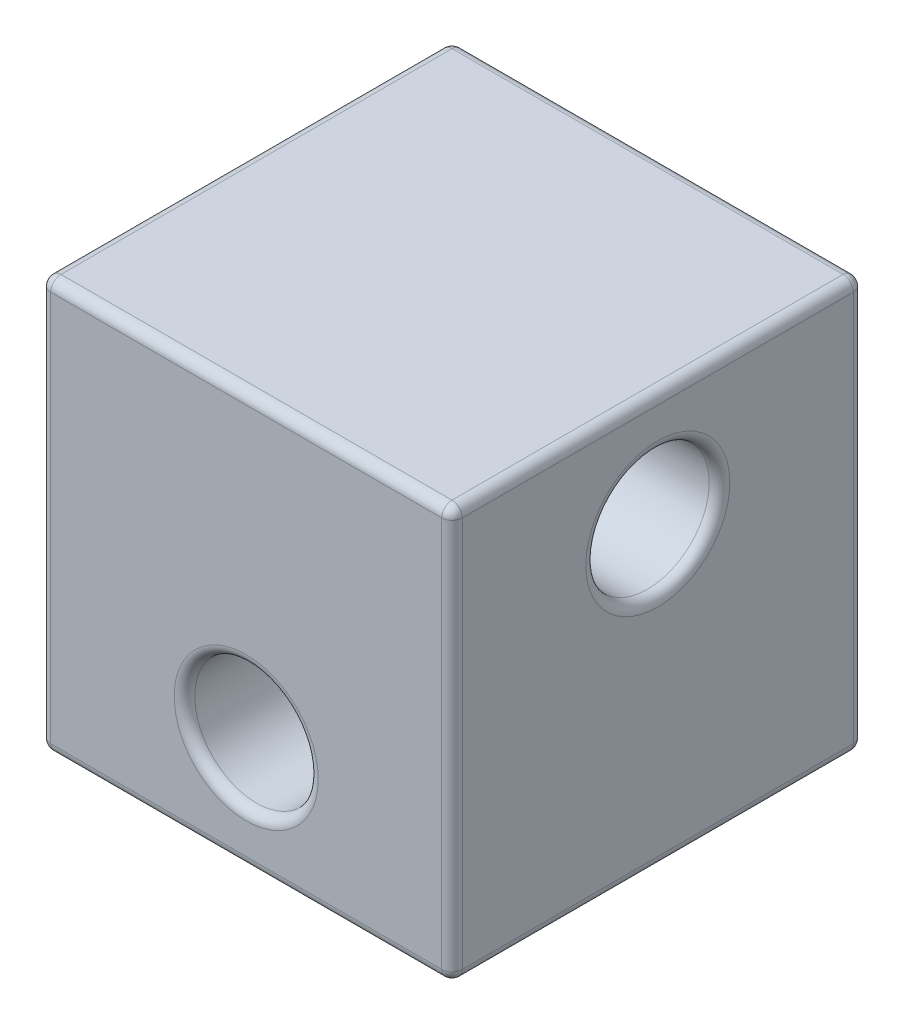
SolidWorks part; units mm, degrees
ref_plane "Front Plane" through (0, 0, 0) normal (0, 0, 1) x (1, 0, 0)
ref_plane "Top Plane" through (0, 0, 0) normal (0, 1, 0) x (1, 0, 0)
ref_plane "Right Plane" through (0, 0, 0) normal (1, 0, 0) x (0, 0, -1)
sketch "Sketch1" plane through (0, 0, 0) normal (0, 0, 1) x (1, 0, 0)
  line L1 (-20, 20) -> (20, 20)
  line L2 (-20, 20) -> (-20, -20)
  line L3 (-20, -20) -> (20, -20)
  line L4 (20, 20) -> (20, -20)
  line L5 (-20, 20) -> (20, -20) construction
  line L6 (-20, -20) -> (20, 20) construction
  point P0 (0, 0)
  dimension "D1" = 40
  dimension "D2" = 40
extrude "Boss-Extrude1" add sketch "Sketch1" along normal mid plane 40
sketch "Sketch2" plane through (0, 0, 20) normal (0, 0, 1) x (1, 0, 0)
  line L0 (0, 13.6388) -> (0, -9.4213) construction
  circle A0 centre (0, -9) radius 6
  dimension "D1" = 12
  dimension "D2" = 9
extrude "Cut-Extrude1" cut sketch "Sketch2" against normal through all
sketch "Sketch3" plane through (-20, 0, 0) normal (-1, 0, 0) x (0, 0, 1)
  line L0 (0, 17.6012) -> (0, -12.9076) construction
  circle A0 centre (0, 9) radius 6
  dimension "D1" = 12
  dimension "D2" = 9
extrude "Cut-Extrude2" cut sketch "Sketch3" against normal through all
fillet "Fillet1" radius 1 16 edges at (0, -20, -20) (20, -20, 0) (20, 0, -20) (20, 3, 0) (20, 20, 0) (0, 20, -20) (0, -20, 20) (0, 20, 20) (20, 0, 20) (6, -9, 20) (-20, 20, 0) (-20, 0, 20) (-20, -20, 0) (-20, 0, -20) (-20, 3, 0) (6, -9, -20)
